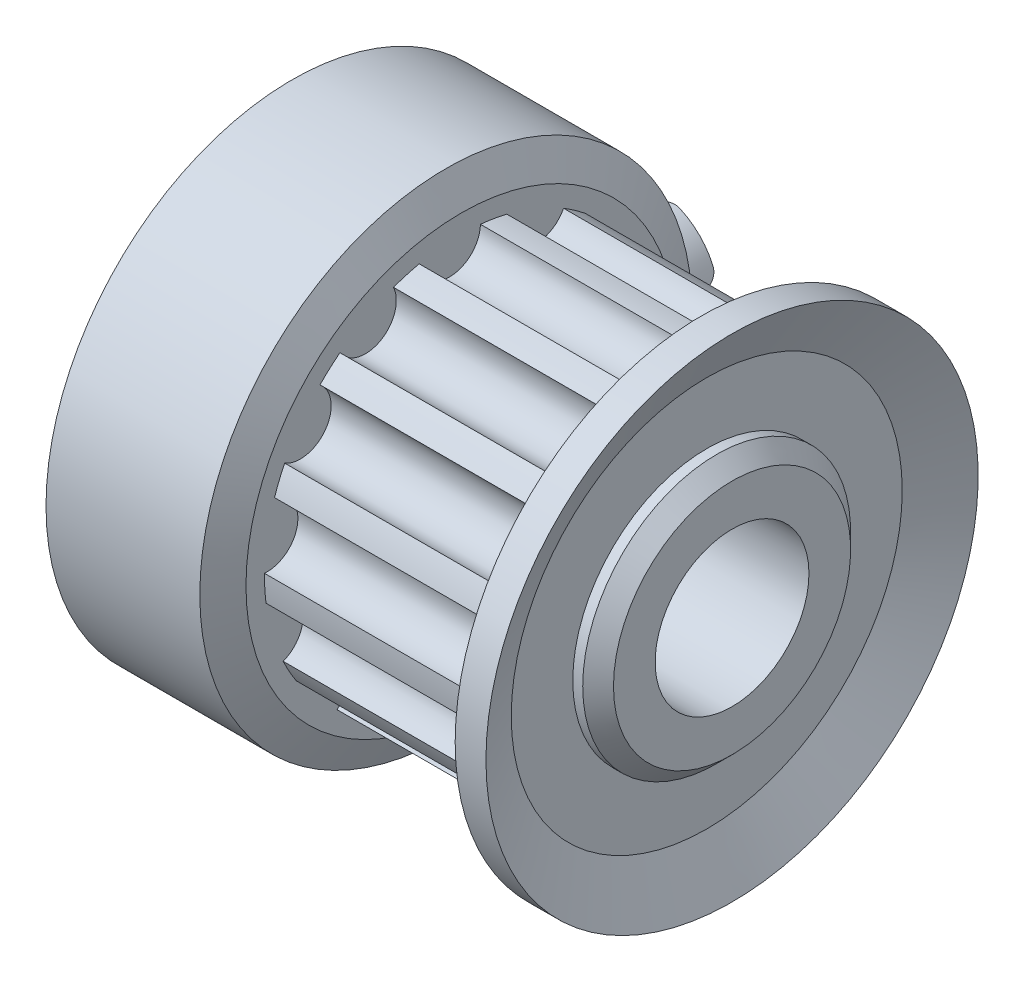
SolidWorks part; units mm, degrees
ref_plane "Front Plane" through (0, 0, 0) normal (0, 0, 1) x (1, 0, 0)
ref_plane "Top Plane" through (0, 0, 0) normal (0, 1, 0) x (1, 0, 0)
ref_plane "Right Plane" through (0, 0, 0) normal (1, 0, 0) x (0, 0, -1)
sketch "Sketch2" plane through (0, 0, 0) normal (0, 0, 1) x (1, 0, 0)
  line L0 (0, 8.3422) -> (0, 1.3422) construction
  line L1 (0, 1.3422) -> (14.8, 1.3422) construction
  line L2 (0, 8.3422) -> (0, 5.2422)
  line L3 (0.1, 5.1422) -> (0.3, 5.1422)
  line L4 (0.3, 5.1422) -> (0, 4.8422)
  line L5 (0, 4.8422) -> (0, 1.3422)
  line L6 (0, 1.3422) -> (14.8, 1.3422)
  line L10 (0, 8.3422) -> (0.5, 9.3422)
  line L11 (0.5, 9.3422) -> (5.5, 9.3422)
  line L13 (6, 8.3422) -> (6, 7.7422)
  line L14 (6, 7.7422) -> (13, 7.7422)
  line L15 (13, 7.7422) -> (13.8, 9.3422)
  line L16 (13.8, 9.3422) -> (14.8, 9.3422)
  line L18 (5.5, 9.3422) -> (6, 8.3422)
  line L19 (14.8, 9.3422) -> (13.9771, 7.6965)
  line L25 (13.9771, 7.6965) -> (13.9771, 5.6965)
  line L26 (13.9771, 5.6965) -> (14.3, 5.6965)
  line L27 (14.8, 5.1965) -> (14.8, 1.3422)
  line L28 (14.3, 5.6965) -> (14.8, 5.1965)
  arc A0 (0, 5.2422) -> (0.1, 5.1422) centre (0.1, 5.2422) ccw
  point P19 (0, 5.1422)
  point P22 (14.8, 5.6965)
  dimension "D12" = 0.1
  dimension "D1" = 14.8
  dimension "D2" = 14.8
  dimension "D3" = 8
  dimension "D4" = 8
  dimension "D5" = 5
  dimension "D6" = 6
  dimension "D7" = 0.5
  dimension "D8" = 1
  dimension "D9" = 3.2
  dimension "D10" = 0.3
  dimension "D11" = 0.3
  dimension "D13" = 7
  dimension "D14" = 1
  dimension "D15" = 1.84
  dimension "D16" = 2
revolve "Revolve1" add sketch "Sketch2" angle 360 about L6
sketch "Sketch3" plane through (14.8, 0, 0) normal (1, 0, 0) x (0, 0, -1)
  circle A0 centre (0, 1.3422) radius 2.5
  dimension "D1" = 5
extrude "Cut-Extrude1" cut sketch "Sketch3" against normal through all
sketch "Sketch4" plane through (6, 0, 0) normal (1, 0, 0) x (0, 0, -1)
  line L0 (0, 1.3422) -> (-10.1084, 1.6548) construction
  circle A0 centre (4.7585, 5.622) radius 1
  circle A1 centre (0, 1.3422) radius 6.4 construction
  circle A2 centre (6.1442, 3.1335) radius 1
  circle A3 centre (6.3129, 0.2902) radius 1
  circle A4 centre (5.2313, -2.3447) radius 1
  circle A5 centre (3.1136, -4.2494) radius 1
  circle A6 centre (0.3792, -5.0466) radius 1
  circle A7 centre (-2.4304, -4.5784) radius 1
  circle A8 centre (-4.7585, -2.9376) radius 1
  circle A9 centre (-6.1442, -0.4491) radius 1
  circle A10 centre (-6.3129, 2.3942) radius 1
  circle A11 centre (-5.2313, 5.0291) radius 1
  circle A12 centre (-3.1136, 6.9338) radius 1
  circle A13 centre (-0.3792, 7.731) radius 1
  circle A14 centre (2.4304, 7.2628) radius 1
  point P38 (0, 1.3422)
  dimension "D1" = 2
  dimension "D2" = 14
extrude "Cut-Extrude2" cut sketch "Sketch4" along normal up to surface (7.3874 mm away) up to face at (13, 1.3422, 6.4)
sketch "Sketch5" plane through (0, 0, 0) normal (0, 0, 1) x (1, 0, 0)
  line L0 (0.5, 9.3422) -> (0.5, -6.6578) construction
  circle A0 centre (3.5, 1.3422) radius 1.5
  dimension "D1" = 3
  dimension "D2" = 3
extrude "Cut-Extrude3" cut sketch "Sketch5" against normal through all
fillet "Fillet1" radius 0.2 1 edges at (2.0336, 1.0266, -7.9938)
scale "Scale1" scale about centroid uniform scaling yes scale factor 2.4
ref_plane "Plane1" through (0, 0, -19.2) normal (0, 0, 1) x (1, 0, 0)
sketch "Sketch6" plane through (0, 0, -19.2) normal (0, 0, 1) x (1, 0, 0)
  circle A0 centre (-0.538, 1.3422) radius 3.6 construction
  circle A1 centre (-0.538, 1.3422) radius 3.6
extrude "Boss-Extrude1" add sketch "Sketch6" along normal blind 11 separate body
sketch "Sketch7" plane through (0, 0, -8.2) normal (0, 0, 1) x (1, 0, 0)
  circle A0 centre (-0.538, 1.3422) radius 5
  dimension "D1" = 10
extrude "Boss-Extrude2" add sketch "Sketch7" along normal blind 2
sketch "Sketch10" plane through (0, 0, -19.2) normal (0, 0, -1) x (-1, 0, 0)
  circle A0 centre (0.538, 1.3422) radius 5
  dimension "D1" = 10
extrude "Boss-Extrude5" add sketch "Sketch10" along normal blind 2
sketch "Sketch11" plane through (0, 0, -21.2) normal (0, 0, -1) x (-1, 0, 0)
  line L0 (-0.462, 2.3422) -> (-0.462, 7.4239)
  line L1 (-0.462, -4.7395) -> (1.538, -4.7395)
  line L2 (-0.462, -4.7395) -> (-0.462, 0.3422)
  line L3 (-0.462, 7.4239) -> (1.538, 7.4239)
  line L4 (1.538, -4.7395) -> (1.538, 0.3422)
  line L7 (-5.7812, 0.3422) -> (-0.462, 0.3422)
  line L8 (-5.7812, 0.3422) -> (-5.7812, 2.3422)
  line L9 (-5.7812, 2.3422) -> (-0.462, 2.3422)
  line L10 (6.8572, 0.3422) -> (6.8572, 2.3422)
  line L16 (1.538, 2.3422) -> (6.8572, 2.3422)
  line L17 (1.538, 2.3422) -> (1.538, 7.4239)
  line L19 (1.538, 0.3422) -> (6.8572, 0.3422)
  point P0 (0.538, 1.3422)
  point P6 (0.538, 1.3422)
  dimension "D1" = 2
  dimension "D2" = 2
extrude "Cut-Extrude4" cut sketch "Sketch11" against normal blind 1
fillet "Fillet2" radius 1 4 edges at (2.4115, 2.3422, -21.2) (-3.4874, 2.3422, -21.2) (-1.538, 4.2917, -21.2) (0.462, 4.2917, -21.2)
fillet "Fillet3" radius 1 4 edges at (-1.538, -1.6073, -21.2) (-3.4874, 0.3422, -21.2) (0.462, -1.6073, -21.2) (2.4115, 0.3422, -21.2)
fillet "Fillet4" radius 0.1 2 edges at (-0.538, -3.6578, -19.2) (-0.538, 6.3422, -19.2)
